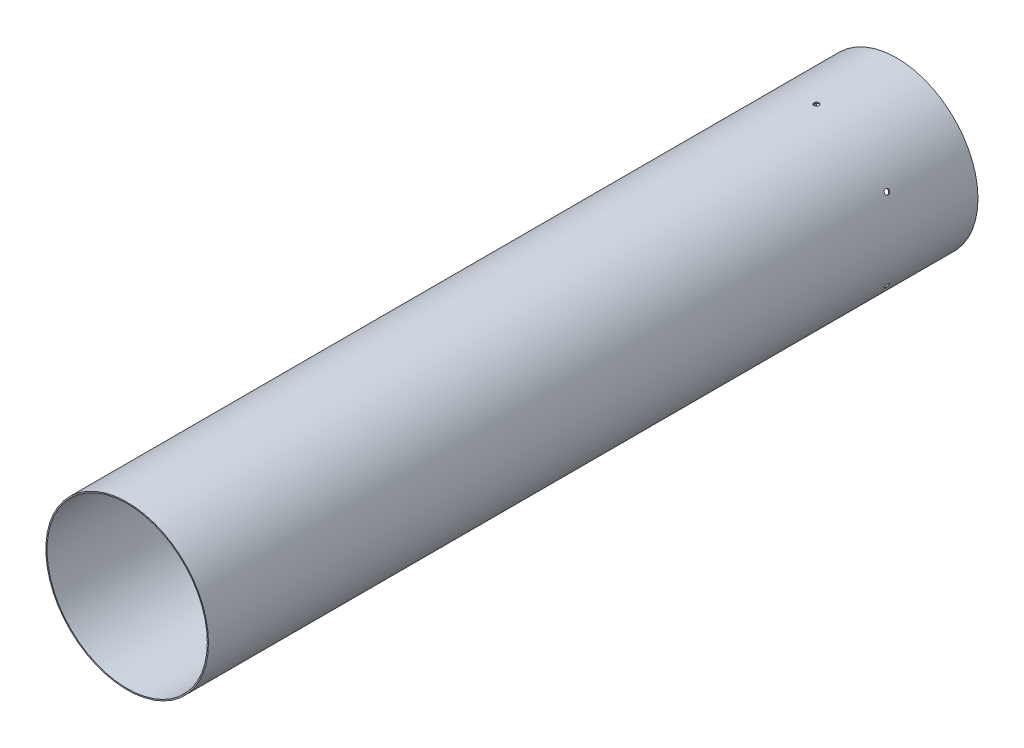
SolidWorks part; units mm, degrees
ref_plane "Front Plane" through (0, 0, 0) normal (0, 0, 1) x (1, 0, 0)
ref_plane "Top Plane" through (0, 0, 0) normal (0, 1, 0) x (1, 0, 0)
ref_plane "Right Plane" through (0, 0, 0) normal (1, 0, 0) x (0, 0, -1)
sketch "Sketch1" plane through (0, 0, 0) normal (0, 0, 1) x (1, 0, 0)
  circle A0 centre (0, 0) radius 79.375
  circle A1 centre (0, 0) radius 80.518
  dimension "D1" = 158.75
  dimension "D2" = 1.143
extrude "Boss-Extrude1" add sketch "Sketch1" along normal blind 762
ref_plane "Plane1" through (0, 80.518, 0) normal (0, 1, 0) x (1, 0, 0)
sketch "Sketch2" plane through (0, 80.518, 0) normal (0, 1, 0) x (1, 0, 0)
  line L0 (79.375, 0) -> (-79.375, 0) construction
  point P0 (0, -79.375)
  dimension "D1" = 79.375
hole_wizard "#10 (0.1935) Diameter Hole1" positions "Sketch3" profile "Sketch4" hole size "#10" standard "ANSI Inch" end condition up to next
sketch "Sketch3" plane through (0, 80.518, 0) normal (0, 1, 0) x (1, 0, 0)
  point P0 (0, -79.375)
sketch "Sketch4" plane through (0, 80.518, 79.375) normal (1, 0, 0) x (0, 0, 1)
  line L0 (0, 0) -> (0, 1.143)
  line L1 (0, 1.143) -> (2.4574, 1.143)
  line L2 (2.4574, 1.143) -> (2.4574, 0)
  line L5 (2.4574, 0) -> (0, 0)
  line L11 (0, -6.35) -> (0, 107.95) construction
  dimension "Thru Hole Dia." = 4.9149
  dimension "Thru Hole Depth" = 1.143
pattern_circular "CirPattern1" count 6 over 360 about axis through (0, 0, 0) along (0, 0, 1) of "#10 (0.1935) Diameter Hole1"
